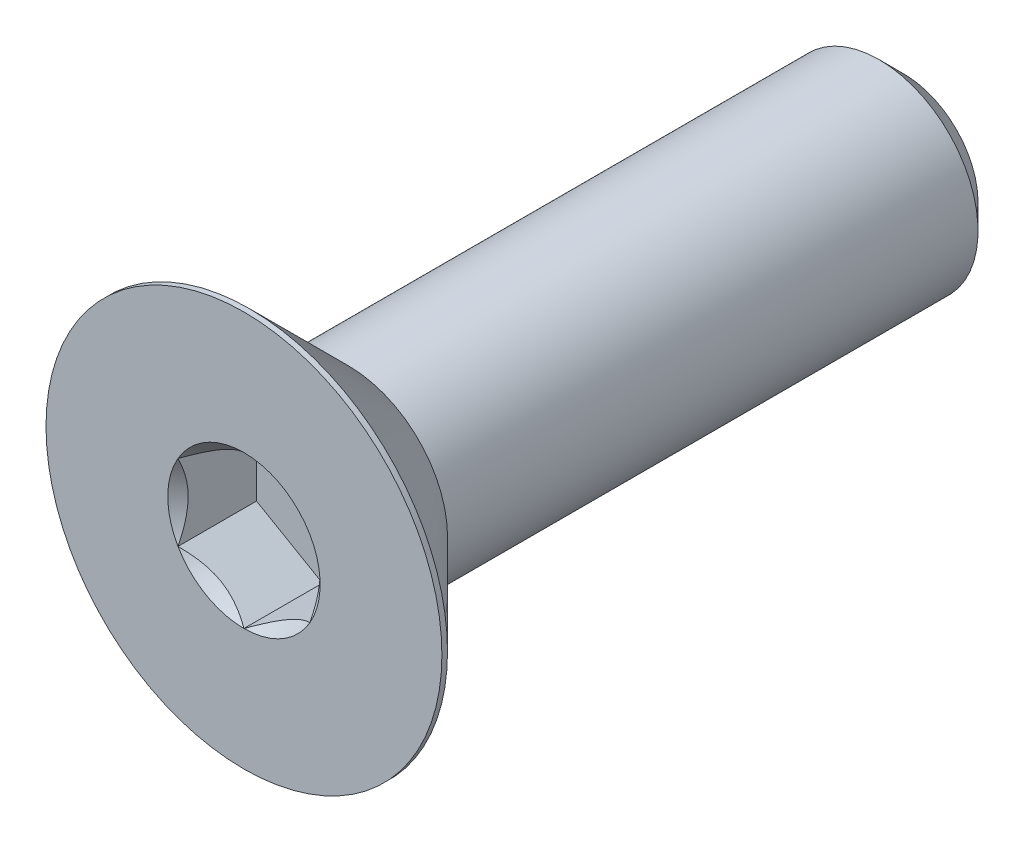
SolidWorks part; units mm, degrees
ref_plane "Front" through (0, 0, 0) normal (0, 0, 1) x (1, 0, 0)
ref_plane "Top" through (0, 0, 0) normal (0, 1, 0) x (1, 0, 0)
ref_plane "Right" through (0, 0, 0) normal (1, 0, 0) x (0, 0, -1)
sketch "Sketch11" plane through (0, 0, 0) normal (1, 0, 0) x (0, 0, -1)
  line L0 (-5, 3) -> (5, 3) construction
  line L5 (-5, 3) -> (-5, -3) construction
  line L6 (5, 1.5) -> (5, -1.5) construction
  line L7 (-4.99, 1) -> (-4.99, -1) construction
  line L8 (4.9688, 1.5541) -> (5.4688, 1.5541) construction
  line L9 (5.4688, 1.5541) -> (5.2188, 1.1211) construction
  line L10 (5.2188, 1.1211) -> (4.9688, 1.5541) construction
  line L11 (5.1875, 1.1752) -> (5.25, 1.1752) construction
  line L12 (5.2188, 1.1752) -> (5.2188, 1.1211) construction
  line L13 (4.9844, 1.5271) -> (5.4531, 1.5271) construction
  line L14 (5.2188, 1.5541) -> (5.2188, 1.5) construction
  line L15 (5, 1.5) -> (5.4375, 1.5) construction
  line L17 (-4.915, 3) -> (-1.915, 0) construction
  line L18 (-1.915, 0) -> (-4.915, -3) construction
  point P3 (-3.3, 3)
  point P8 (0, 3)
  point P21 (5.2188, 1.5271)
  point P26 (-5, 0)
  point P28 (-4.99, 0)
  point P29 (5, 0)
  dimension "Length" = 10
  dimension "Head Diameter" = 6
  dimension "Thread Major Diameter" = 3
  dimension "Head Height" = 1.7
  dimension "Drive Size" = 2
  dimension "Thread Pitch" = 0.5
  dimension "D1" = 0.0625
  dimension "D2" = 0.01
  dimension "D3" = 0.085
  dimension "Countersink Angle" = 90
sketch "Sketch1" plane through (0, 0, 0) normal (1, 0, 0) x (0, 0, -1)
  line L2 (-3.3, 1.5) -> (5, 1.5)
  line L3 (5, 1.5) -> (5, 0)
  line L4 (-3.81, 1.5) -> (-3.81, 0)
  line L5 (-3.3, 1.5) -> (-3.81, 1.5)
  line L6 (-5, 3) -> (-5, -3) construction
  line L7 (5, 1.5) -> (5, -1.5) construction
  line L8 (-3.81, 0) -> (5, 0)
  dimension "D1" = 1.19
revolve "Revolve1" add sketch "Sketch1" angle 360 mid plane about L8
chamfer "Chamfer1" distance 0.375 angle 45 1 edges at (0, -1.5, -5)
sketch "Sketch7" plane through (0, 0, 0) normal (1, 0, 0) x (0, 0, -1)
  line L2 (-5, 3) -> (-4.915, 3)
  line L5 (-3.3, 1.385) -> (-3.3, 0)
  line L6 (-5, 3) -> (-5, 0)
  line L8 (-5, 3) -> (-5, -3) construction
  line L9 (-5, 0) -> (-3.3, 0)
  line L12 (-4.915, 3) -> (-3.3, 1.385)
  line L13 (-4.915, 3) -> (-1.915, 0) construction
revolve "Revolve2" add sketch "Sketch7" angle 360 mid plane about L9 region at (0, 1.1696, 4.2571)
ref_plane "Plane1" through (0, 0, 3.3) normal (0, 0, 1) x (1, 0, 0)
sketch "Sketch5" plane through (0, 0, 5) normal (0, 0, 1) x (1, 0, 0)
  line L1 (1, -0.5774) -> (1, 0.5774)
  line L2 (1, 0.5774) -> (0, 1.1547)
  line L3 (0, 1.1547) -> (-1, 0.5774)
  line L4 (-1, 0.5774) -> (-1, -0.5774)
  line L5 (-1, -0.5774) -> (0, -1.1547)
  line L6 (0, -1.1547) -> (1, -0.5774)
  circle A0 centre (0, 0) radius 1 construction
extrude "Cut-Extrude2" cut sketch "Sketch5" against normal blind 1.19
sketch "Sketch6" plane through (0, 0, 5) normal (0, 0, -1) x (-1, 0, 0)
  circle A0 centre (0, 0) radius 1.1547
extrude "Cut-Extrude3" cut sketch "Sketch6" along normal blind 1.19 draft 45
sketch "Sketch12" [suppressed] plane through (0, 0, -5) normal (0, 0, -1) x (-1, 0, 0)
  circle A0 centre (0, 0) radius 1.5 construction
  circle A1 centre (0, 0) radius 1.5
curve "Helix/Spiral1" [suppressed] pitch 0.5 height 10 turns 20
sketch "Sketch13" [suppressed] plane through (0, 0, 0) normal (1, 0, 0) x (0, 0, -1)
  line L0 (4.9844, 1.5271) -> (5.4531, 1.5271)
  line L1 (5.4531, 1.5271) -> (5.25, 1.1752)
  line L2 (5.25, 1.1752) -> (5.1875, 1.1752)
  line L3 (5.1875, 1.1752) -> (4.9844, 1.5271)
sweep "Cut-Sweep1" [suppressed] cut profiles "Sketch13" path "Helix/Spiral1"
combine bodies "Combine1" [suppressed] operation type add bodies to combine 113 127
equation "\"D1@Chamfer1\"=\"Thread Pitch@Sketch11\" * .75"
equation "\"D1@Cut-Extrude2\"= \"Head Height@Sketch11\" * .7"
equation "\"D1@Cut-Extrude3\" = \"D1@Cut-Extrude2\""
equation "\"D1@Sketch11\"=\"Thread Pitch@Sketch11\"/8"
equation "\"D3@Sketch11\"=\"Head Height@Sketch11\"*.05"
equation "\"D4@Helix/Spiral1\"=\"Thread Pitch@Sketch11\""
equation "\"D1@Sketch1\"=\"Head Height@Sketch11\"*.7"
equation "\"D3@Helix/Spiral1\"=\"Length@Sketch11\""
